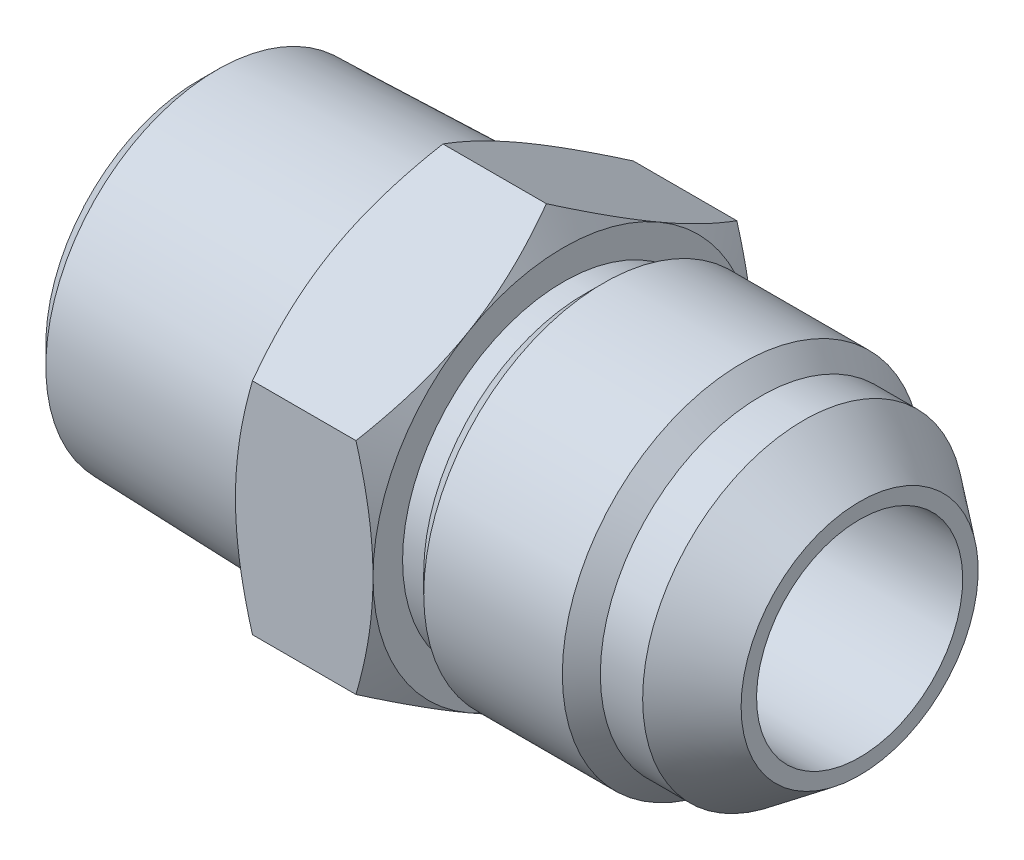
SolidWorks part; units mm, degrees
ref_plane "Front" through (0, 0, 0) normal (0, 0, 1) x (1, 0, 0)
ref_plane "Top" through (0, 0, 0) normal (0, 1, 0) x (1, 0, 0)
ref_plane "Right" through (0, 0, 0) normal (1, 0, 0) x (0, 0, -1)
sketch "Sketch6" plane through (0, 0, 0) normal (0, 0, 1) x (1, 0, 0)
  line L0 (-7.7406, 13.335) -> (-7.7406, -13.335) construction
  line L1 (24.8031, 13.4937) -> (24.8031, -13.4937) construction
  line L2 (-24.8031, 0) -> (24.8031, 0)
  line L4 (-24.8031, 0) -> (-24.8031, 13.4938)
  line L5 (-24.8031, 13.4938) -> (24.8031, 13.4937)
  line L6 (24.8031, 0) -> (24.8031, 13.4937)
  point P4 (2.5781, 0)
  point P6 (-7.7406, 0)
  dimension "Straight Dia" = 26.9875
  dimension "Length" = 49.6062
  dimension "L1" = 22.225
  dimension "Pipe OD" = 26.67
  dimension "Pipe Thread Length" = 17.0624
revolve "Revolve3" add sketch "Sketch6" angle 360 about L2
sketch "Sketch14" plane through (24.8031, 0, 0) normal (-1, 0, 0) x (0, 0, 1)
  circle A1 centre (0, 0) radius 13.4938
  circle A2 centre (0, 0) radius 13.4938
  dimension "D1" = 0
curve "Helix/Spiral1" pitch 2.1167 height 24.3417 turns 11.5 parameters "Pitch"=2.1167
sketch "Sketch15" plane through (0, 0, 0) normal (0, 0, 1) x (1, 0, 0)
  line L0 (24.8031, 13.4938) -> (26.6552, 13.4937)
  line L1 (26.6552, 13.4937) -> (25.8614, 12.1189)
  line L2 (25.8614, 12.1189) -> (25.5968, 12.1189)
  line L3 (25.5968, 12.1189) -> (24.8031, 13.4938)
  line L4 (25.7291, 12.1189) -> (25.7291, 13.4938) construction
  line L5 (25.2, 12.8063) -> (26.2583, 12.8063) construction
  dimension "D1" = 60
  dimension "D2" = 0.2646
  dimension "D3" = 1.0583
sweep "Cut-Sweep1" [suppressed] cut profiles "Sketch15" path "Helix/Spiral1"
ref_plane "Plane1" through (-7.7406, 0, 0) normal (1, 0, 0) x (0, 0, -1)
sketch "Sketch12" plane through (-7.7406, 0, 0) normal (1, 0, 0) x (0, 0, -1)
  line L1 (0, 16.4978) -> (-14.2875, 8.2489)
  line L2 (-14.2875, 8.2489) -> (-14.2875, -8.2489)
  line L3 (-14.2875, -8.2489) -> (0, -16.4978)
  line L4 (0, -16.4978) -> (14.2875, -8.2489)
  line L5 (14.2875, -8.2489) -> (14.2875, 8.2489)
  line L6 (14.2875, 8.2489) -> (0, 16.4978)
  circle A0 centre (0, 0) radius 14.2875 construction
  dimension "Hex" = 28.575
extrude "Extrude1" add sketch "Sketch12" along normal up to vertex (10.3187 mm away) up to point (2.5781, 0, 0)
sketch "Sketch7" plane through (0, 0, 0) normal (0, 0, 1) x (1, 0, 0)
  line L0 (-24.8031, 0) -> (-24.8031, 7.7343)
  line L2 (-24.8031, 7.7343) -> (24.8031, 7.7343)
  line L4 (24.8031, 0) -> (24.8031, 13.4937) construction
  line L11 (24.8031, 7.7343) -> (24.8031, 0)
  line L12 (24.8031, 0) -> (-24.8031, 0)
  line L13 (-24.8031, 7.7343) -> (-24.8031, -7.7343) construction
  dimension "ID" = 15.4686
sketch "Sketch10" plane through (0, 0, 0) normal (0, 0, 1) x (1, 0, 0)
  line L0 (-24.8031, 13.4938) -> (24.8031, 13.4937) construction
  line L1 (24.8031, 13.4938) -> (26.6552, 13.4937) construction
  line L3 (2.5781, 16.4978) -> (2.5781, 8.2489) construction
  line L5 (0, 0) -> (-24.8031, 0) construction
  line L6 (5.5912, 13.4938) -> (2.5781, 13.4937)
  line L9 (2.5781, 12.0681) -> (2.5781, 13.4937)
  line L21 (24.8031, 13.4938) -> (15.9909, 13.4937)
  line L22 (15.9909, 13.4937) -> (17.4165, 12.0681)
  line L23 (17.4165, 12.0681) -> (20.5915, 12.0681)
  line L24 (20.5915, 12.0681) -> (24.8031, 8.8944)
  line L25 (24.8031, 8.8944) -> (24.8031, 13.4938)
  line L26 (4.1656, 12.0681) -> (2.5781, 12.0681)
  line L27 (5.5912, 13.4938) -> (4.1656, 12.0681)
  point P5 (13.1831, -13.4937)
  point P9 (-10.4026, -7.1438)
  point P24 (-10.4026, 0)
  dimension "D1" = 17.7889
  dimension "D2" = 37
  dimension "D3" = 3.175
  dimension "D5" = 45
  dimension "D4" = 1.5875
  dimension "D6" = 4.2333
  dimension "D7" = 0.0508
revolve "Cut-Revolve6" cut sketch "Sketch10" angle 360 about L2
revolve "Cut-Revolve5" cut sketch "Sketch7" angle 360 about L12
sketch "Sketch13" plane through (0, 0, 0) normal (0, 0, 1) x (1, 0, 0)
  line L0 (-7.7406, 16.4978) -> (-7.7406, 14.2875)
  line L1 (-7.7406, 8.2489) -> (-7.7406, 16.4978) construction
  line L2 (-7.7406, 14.2875) -> (-6.4645, 16.4978)
  line L3 (-6.4645, 16.4978) -> (-7.7406, 16.4978)
  line L4 (1.302, 16.4978) -> (2.5781, 14.2875)
  line L5 (2.5781, 16.4978) -> (2.5781, 8.2489) construction
  line L6 (2.5781, 14.2875) -> (2.5781, 16.4978)
  line L7 (2.5781, 16.4978) -> (1.302, 16.4978)
  dimension "D2" = 30
revolve "Cut-Revolve7" cut sketch "Sketch13" angle 360 about L2
sketch "Sketch17" plane through (-24.8031, 0, 0) normal (-1, 0, 0) x (0, 0, 1)
  circle A0 centre (0, 0) radius 13.4938 construction
  circle A1 centre (0, 0) radius 13.4938
extrude "Cut-Extrude1" cut sketch "Sketch17" against normal up to vertex (17.0624 mm away) up to point (-7.7406, 0, 0)
ref_plane "Plane2" through (-7.7406, 0, 0) normal (1, 0, 0) x (0, 0, -1)
sketch "Sketch19" plane through (-7.7406, 0, 0) normal (1, 0, 0) x (0, 0, -1)
  circle A0 centre (0, 0) radius 13.335
extrude "Boss-Extrude1" add sketch "Sketch19" against normal up to vertex (17.0624 mm away) draft 1.75 separate body up to point (-24.8031, 0, 0)
sketch "Sketch20" plane through (-24.8031, 0, 0) normal (1, 0, 0) x (0, 0, -1)
  circle A1 centre (0, 0) radius 12.8137
  circle A2 centre (0, 0) radius 12.8137 construction
sketch "Sketch21" plane through (0, 0, 0) normal (0, 0, 1) x (1, 0, 0)
  line L0 (-26.4093, 12.6936) -> (-24.8724, 12.6936) construction
  line L1 (-26.548, 12.9338) -> (-25.6409, 11.3626) construction
  line L2 (-25.761, 11.5706) -> (-25.5208, 11.5706)
  line L3 (-25.6409, 11.3626) -> (-24.7338, 12.9338) construction
  line L4 (-25.6409, 11.3626) -> (-25.5208, 11.5706) construction
  line L5 (-25.6409, 12.6936) -> (-25.6409, 12.9338) construction
  line L6 (-26.548, 12.9338) -> (-24.7338, 12.9338) construction
  line L7 (-25.6409, 12.8137) -> (-24.8031, 12.8137) construction
  line L8 (-24.7338, 12.9338) -> (-26.4787, 12.8137)
  line L9 (-26.4787, 12.8137) -> (-25.761, 11.5706)
  line L10 (-25.5208, 11.5706) -> (-24.7338, 12.9338)
  line L11 (-25.6409, 11.3626) -> (-25.6409, 11.5706) construction
  dimension "D2" = 0.2402
  dimension "D1" = 1.8143
curve "Helix/Spiral2" parameters "Pitch"=1.8143
chamfer "Chamfer1" distance 1.3607 angle 45 1 edges at (-24.8031, 0, -12.8137) first distance on face at (-24.8031, 0, -12.8137)
sketch "Sketch22" plane through (-7.7406, 0, 0) normal (1, 0, 0) x (0, 0, -1)
  circle A1 centre (0, 0) radius 13.335
  circle A2 centre (0, 0) radius 13.335
  dimension "D1" = 0
sweep "Cut-Sweep2" [suppressed] cut profiles "Sketch21" path "Helix/Spiral2"
extrude "Boss-Extrude3" add sketch "Sketch22" against normal up to vertex (17.0624 mm away) draft 15 up to point (-24.8031, 13.4938, 0)
combine bodies "Combine1" operation type add bodies to combine 173 169
sketch "Sketch23" plane through (-24.8031, 0, 0) normal (-1, 0, 0) x (0, 0, 1)
  circle A1 centre (0, 0) radius 10.691
  circle A2 centre (0, 0) radius 10.691
  dimension "D1" = 0.762
extrude "Cut-Extrude2" cut sketch "Sketch23" against normal up to vertex (17.0624 mm away) up to point (-7.7406, 0, 0)
other "CPoint1" parameters "Diameter"=19.05, "StubLength"=0
ref_axis "Axis1" through (34.8031, 0, 0) along (-1, 0, 0)
equation "\"D3@Helix/Spiral1\" = \"L1@Sketch6\"+\"Pitch@Helix/Spiral1\""
equation "\"D2@Sketch15\" = \"Pitch@Helix/Spiral1\"*.125"
equation "\"D3@Sketch15\" = \"Pitch@Helix/Spiral1\"*.5"
equation "\"D3@Sketch10\" = \"Pitch@Helix/Spiral1\"*1.5"
equation "\"D1@Sketch10\" = \"ID@Sketch7\"*1.15"
equation "\"D1@Sketch21\" = \"Pitch@Helix/Spiral2\""
equation "\"D3@Helix/Spiral2\" = \"Pipe Thread Length@Sketch6\"+\"Pitch@Helix/Spiral2\""
equation "\"D1@Chamfer1\" = \"Pitch@Helix/Spiral2\"*.75"
equation "\"D4@Sketch10\" = \"Pitch@Helix/Spiral1\"*.75"
equation "\"D6@Sketch10\" = \"Pitch@Helix/Spiral1\"*2"
